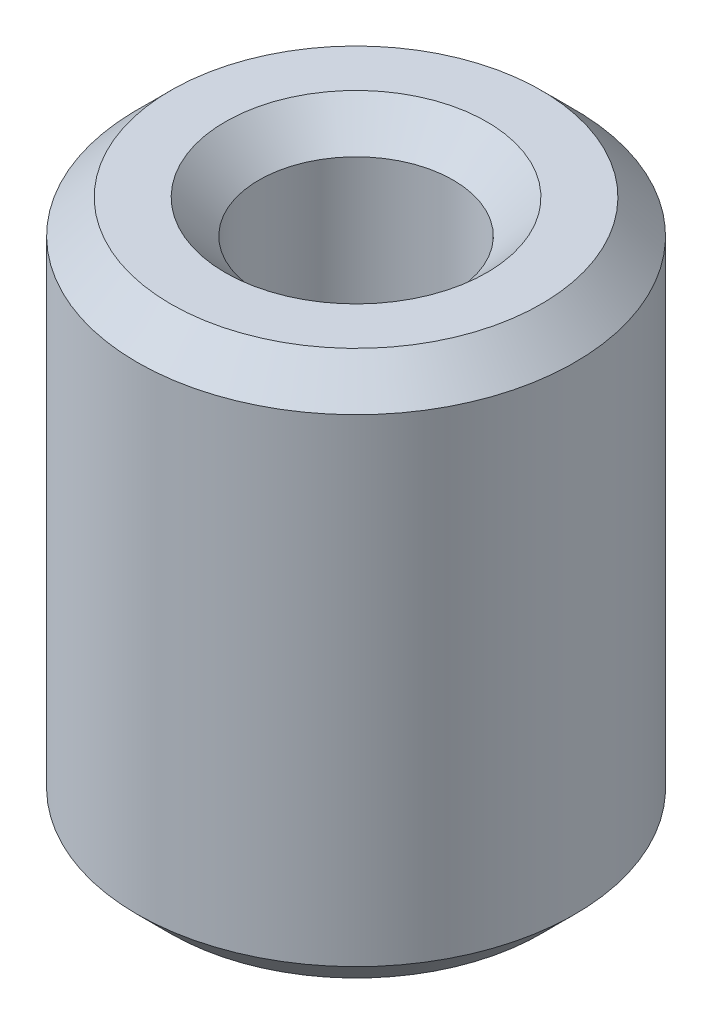
SolidWorks part; units mm, degrees
ref_plane "Front Plane" through (0, 0, 0) normal (0, 0, 1) x (1, 0, 0)
ref_plane "Top Plane" through (0, 0, 0) normal (0, 1, 0) x (1, 0, 0)
ref_plane "Right Plane" through (0, 0, 0) normal (1, 0, 0) x (0, 0, -1)
sketch "Sketch1" plane through (0, 0, 0) normal (0, 1, 0) x (1, 0, 0)
  circle A0 centre (0, 0) radius 17.5
  dimension "SLEEVE_OD" = 35
extrude "Boss-Extrude1" add sketch "Sketch1" along normal blind 43.6093
sketch "Sketch2" plane through (0, 0, 0) normal (0, 1, 0) x (1, 0, 0)
  circle A0 centre (0, 0) radius 7.7649
  dimension "BORE_D" = 15.5298
extrude "Cut-Extrude1" cut sketch "Sketch2" along normal through all
chamfer "Chamfer1" distance 2.6914 angle 45 4 edges at (0, 43.6093, 7.7649) (0, 0, 7.7649) (0, 0, 17.5) (0, 43.6093, 17.5)
